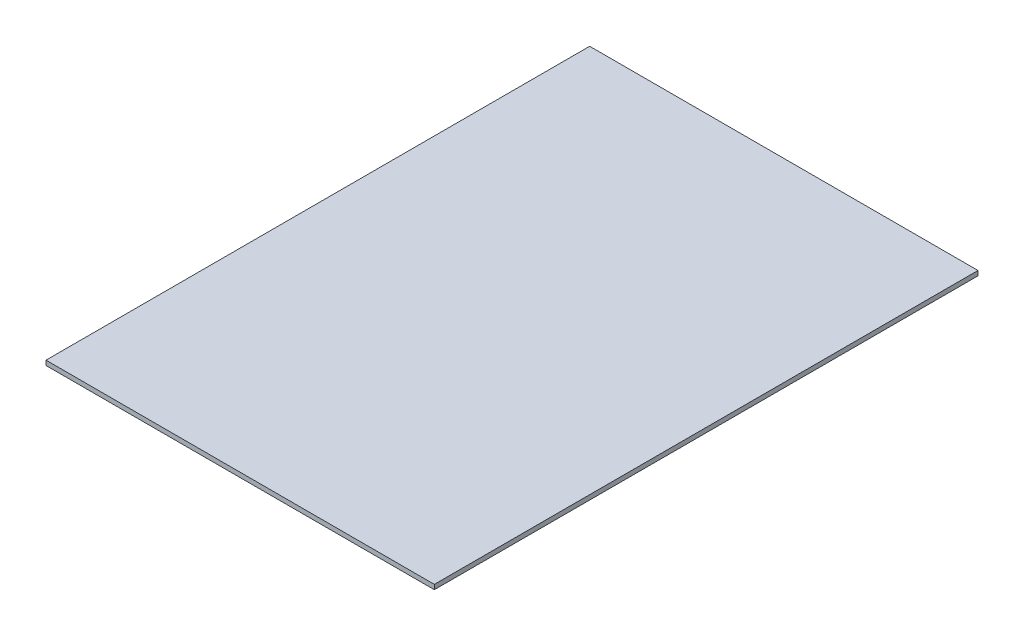
SolidWorks part; units mm, degrees
ref_plane "Front Plane" through (0, 0, 0) normal (0, 0, 1) x (1, 0, 0)
ref_plane "Top Plane" through (0, 0, 0) normal (0, 1, 0) x (1, 0, 0)
ref_plane "Right Plane" through (0, 0, 0) normal (1, 0, 0) x (0, 0, -1)
sketch "Sketch2" plane through (0, 0, 0) normal (0, 1, 0) x (1, 0, 0)
  line L1 (0, 0) -> (250, 0)
  line L2 (0, 0) -> (0, 350)
  line L3 (0, 350) -> (250, 350)
  line L4 (250, 0) -> (250, 350)
  dimension "D1" = 350
  dimension "D2" = 250
extrude "Boss-Extrude1" add sketch "Sketch2" along normal blind 3
